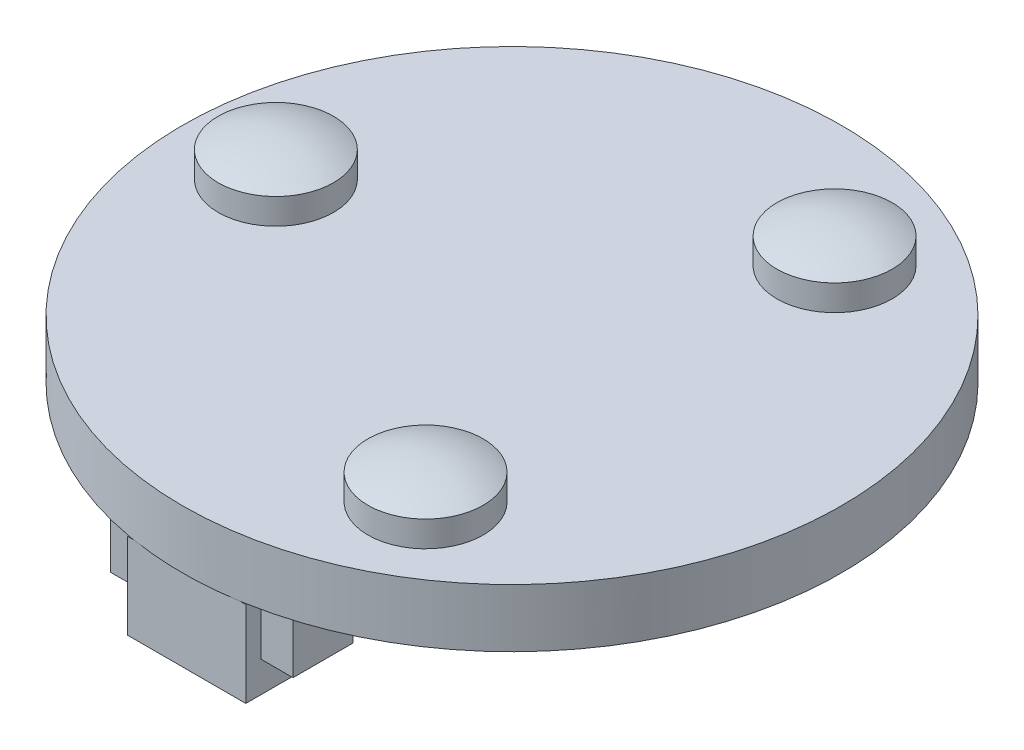
SolidWorks part; units mm, degrees
ref_plane "Front Plane" through (0, 0, 0) normal (0, 0, 1) x (1, 0, 0)
ref_plane "Top Plane" through (0, 0, 0) normal (0, 1, 0) x (1, 0, 0)
ref_plane "Right Plane" through (0, 0, 0) normal (1, 0, 0) x (0, 0, -1)
sketch "Sketch1" plane through (0, 0, 0) normal (0, 1, 0) x (1, 0, 0)
  circle A0 centre (0, 0) radius 15.35
  dimension "D1" = 30.7
extrude "Boss-Extrude1" add sketch "Sketch1" along normal blind 2.71
sketch "Sketch2" plane through (0, 2.71, 0) normal (0, 1, 0) x (-1, 0, 0)
  line L1 (-5.5, 9.5263) -> (0, 0) construction
  line L2 (0, 3.3605) -> (0, -3.3605) construction
  circle A0 centre (-5.5, 9.5263) radius 2.685
  dimension "D1" = 5.37
  dimension "D2" = 11
  dimension "D3" = 30
extrude "Boss-Extrude2" add sketch "Sketch2" along normal blind 1.2
dome "Dome1" faces to dome 1 distance 0.6 reverse direction no elliptical dome no face at (5.5, 3.91, 12.2113) parameters "D1"=0.6
pattern_circular "CirPattern1" count 3 over 360 about axis through (0, 2.71, 0) along (0, 1, 0) of "Dome1", "Boss-Extrude2"
sketch "Sketch3" plane through (0, 0, 0) normal (0, -1, 0) x (1, 0, 0)
  line L0 (0, 15.35) -> (0, -15.35) construction
  line L2 (2.75, 15.15) -> (-2.75, 15.15)
  line L3 (2.75, 15.15) -> (2.75, 10.95)
  line L4 (2.75, 10.95) -> (-2.75, 10.95)
  line L5 (-2.75, 15.15) -> (-2.75, 10.95)
  line L6 (2.75, 15.15) -> (-2.75, 10.95) construction
  line L7 (2.75, 10.95) -> (-2.75, 15.15) construction
  line L8 (-2.75, 13.05) -> (4.4429, 13.05) construction
  line L9 (2.75, 14.45) -> (4.25, 14.45)
  line L10 (4.25, 14.45) -> (4.25, 11.65)
  line L11 (4.25, 11.65) -> (2.75, 11.65)
  line L12 (-4.25, 11.65) -> (-2.75, 11.65)
  line L13 (-4.25, 14.45) -> (-4.25, 11.65)
  line L14 (-2.75, 14.45) -> (-4.25, 14.45)
  line L15 (0, 0) -> (-15.35, 0) construction
  line L16 (2.75, -14.45) -> (4.25, -14.45)
  line L17 (4.25, -14.45) -> (4.25, -11.65)
  line L18 (4.25, -11.65) -> (2.75, -11.65)
  line L19 (2.75, -15.15) -> (2.75, -10.95)
  line L20 (2.75, -10.95) -> (-2.75, -10.95)
  line L21 (-4.25, -11.65) -> (-2.75, -11.65)
  line L22 (-4.25, -14.45) -> (-4.25, -11.65)
  line L23 (-2.75, -14.45) -> (-4.25, -14.45)
  line L24 (-2.75, -15.15) -> (-2.75, -10.95)
  line L25 (2.75, -15.15) -> (-2.75, -15.15)
  line L26 (-1.5955, 10.95) -> (-1.5955, 0) construction
  line L27 (-1.5955, 0) -> (-1.5955, -10.95) construction
  point P4 (0, 13.05)
  point P16 (4.25, 13.05)
  circle M1 centre (0, 0) radius 15.35
  dimension "D1" = 5.5
  dimension "D3" = 4.2
  dimension "D4" = 2.8
  dimension "D5" = 1.5
  dimension "D6" = 21.9
extrude "Boss-Extrude3" add sketch "Sketch3" along normal blind 2.55 contours L2 L5 L4 L3 | L25 L19 L20 L24 | L11 L10 L9 L3 | L5 L14 L13 L12 | L19 L16 L17 L18 | L23 L24 L21 L22 | L3 L2 M1 | L2 L5 M1 | L25 L24 M1 | L25 L19 M1 region at (2.6575, 0, 15.134) region at (0, 0, 13.0488) region at (-2.6575, 0, 15.134) region at (3.5, 0, 13.05) region at (0, 0, -13.0488) region at (2.6575, 0, -15.134) region at (-3.5, 0, 13.05) region at (-2.6575, 0, -15.134) region at (3.5, 0, -13.05) region at (-3.5, 0, -13.05)
sketch "Sketch4" plane through (0, -2.55, 0) normal (0, -1, 0) x (1, 0, 0)
  line L0 (2.75, 10.95) -> (-2.75, 10.95) construction
  line L1 (2.75, 15.15) -> (-2.75, 15.15) construction
  line L2 (2.75, 10.95) -> (-2.75, 10.95)
  line L3 (2.75, 15.15) -> (-2.75, 15.15)
  line L4 (2.75, 15.15) -> (2.75, 10.95)
  line L5 (-2.75, 10.95) -> (-2.75, 15.15)
  line L6 (2.75, -15.15) -> (2.75, -10.95)
  line L7 (2.75, -10.95) -> (-2.75, -10.95)
  line L8 (-2.75, -10.95) -> (-2.75, -15.15)
  line L9 (-2.75, -15.15) -> (2.75, -15.15)
  line L10 (2.75, -15.15) -> (2.7698, -15.1661)
  line M2 (-2.75, 15.15) -> (-2.75, 14.45)
  line M6 (-2.75, 11.65) -> (-2.75, 10.95)
  line M7 (-2.75, 10.95) -> (2.75, 10.95)
  line M8 (2.75, 10.95) -> (2.75, 11.65)
  line M12 (2.75, 14.45) -> (2.75, 15.15)
  line M14 (2.75, 15.15) -> (-2.75, 15.15)
extrude "Boss-Extrude4" add sketch "Sketch4" along normal blind 1.44 contours L5 L4 M6 M7 M8 M12 M14 M2 | L8 L9 L6 L7 region at (0, -2.55, 13.05) region at (0, -2.55, -13.05)
sketch "Sketch5" plane through (0, 0, 0) normal (0, -1, 0) x (1, 0, 0)
  line L0 (-5.1644, -9.426) -> (-2.0166, -2.879)
  line L1 (-2.0166, -2.879) -> (-8.0142, 0.0047)
  line L2 (-8.0142, 0.0047) -> (-11.162, -6.5423)
  line L3 (-11.162, -6.5423) -> (-5.1644, -9.426)
  line L4 (-4.25, -14.45) -> (-4.25, -11.65) construction
  line L5 (-5.1644, -9.426) -> (-5.1644, -14.4552) construction
  line L8 (-2.0166, -2.879) -> (15.0776, -2.879) construction
  arc A0 (-2.75, 15.1017) -> (-2.75, -15.1017) centre (0, 0) ccw construction
  arc A1 (2.75, -15.1017) -> (2.75, 15.1017) centre (0, 0) ccw construction
  dimension "D1" = 6.6548
  dimension "D2" = 7.2644
  dimension "D3" = 5.0292
  dimension "D4" = 0.9144
  dimension "D5" = 17.0942
extrude "Chip" add sketch "Sketch5" along normal blind 1.7018
